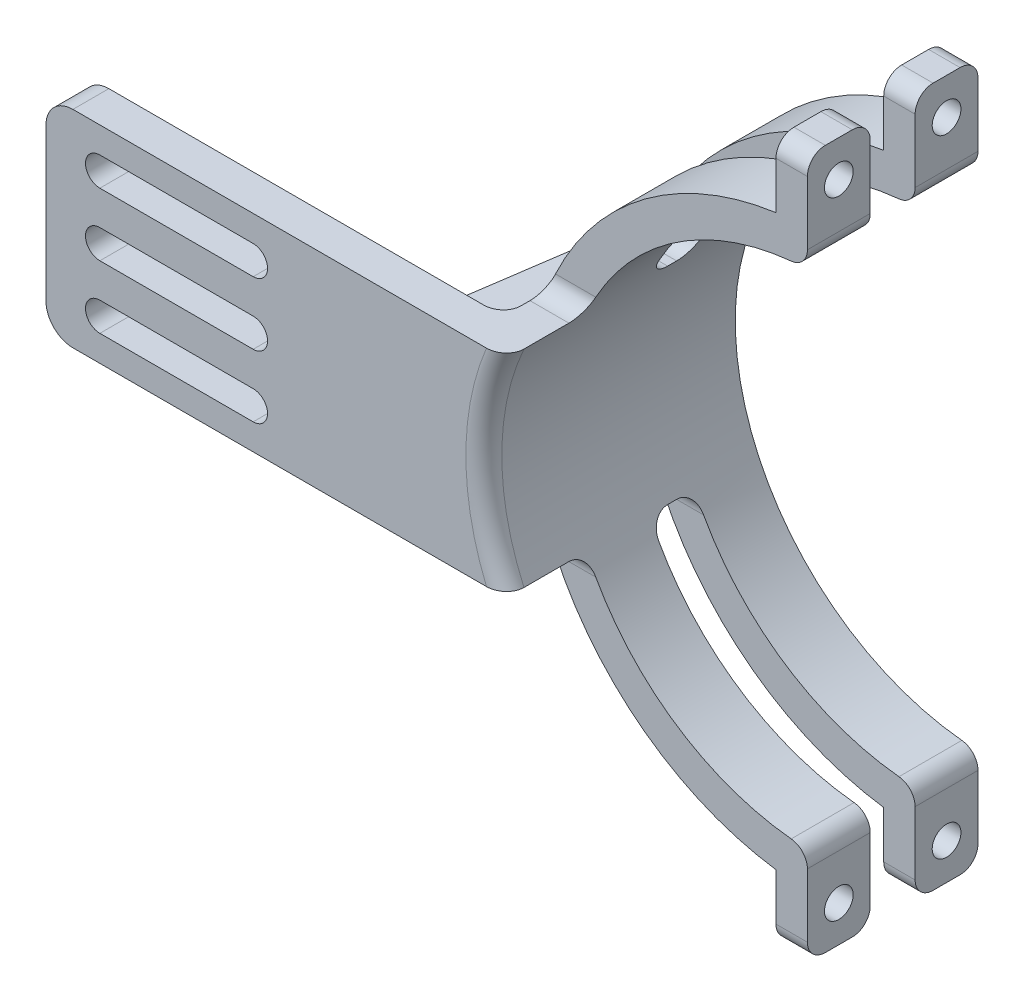
SolidWorks part; units mm, degrees
ref_plane "前视基准面" through (0, 0, 0) normal (0, 0, 1) x (1, 0, 0)
ref_plane "上视基准面" through (0, 0, 0) normal (0, 1, 0) x (1, 0, 0)
ref_plane "右视基准面" through (0, 0, 0) normal (1, 0, 0) x (0, 0, -1)
sketch "草图1" plane through (0, 0, 0) normal (0, 0, 1) x (1, 0, 0)
  line L0 (0, 148.5) -> (0, -94.9538) construction
  line L1 (105, -148.5) -> (-105, -148.5) construction
  line L2 (105, -148.5) -> (105, 148.5) construction
  line L3 (105, 148.5) -> (-105, 148.5) construction
  line L4 (-105, -148.5) -> (-105, 148.5) construction
  line L5 (105, -148.5) -> (-105, 148.5) construction
  line L6 (105, 148.5) -> (-105, -148.5) construction
  line L7 (35.8892, 121.6645) -> (-35.8892, 121.6645)
  line L8 (-35.8892, 121.6645) -> (-66.9017, 102.292)
  line L9 (-75, 40.9339) -> (-75, 31.2613)
  line L10 (-66.9017, 102.292) -> (-66.9017, 52.8701)
  line L11 (75, 40.9339) -> (75, 31.2613)
  line L12 (66.9017, 102.292) -> (66.9017, 52.8701)
  line L13 (35.8892, 121.6645) -> (66.9017, 102.292)
  line L14 (-75, 31.2613) -> (75, 31.2613)
  line L15 (-60, -148.5) -> (-60, -91.8129)
  line L16 (-75, 23.94) -> (75, 23.94)
  line L17 (-75, 23.94) -> (-75, 10.5626)
  line L18 (-38.8455, -105.5906) -> (-66.4608, -113.7617)
  line L19 (-66.4608, -113.7617) -> (-70.1743, -102.7328)
  line L20 (75, 23.94) -> (75, 10.5626)
  line L21 (66.4608, -113.7617) -> (70.1743, -102.7328)
  line L22 (38.8455, -105.5906) -> (66.4608, -113.7617)
  line L23 (-105, 93.0519) -> (105, 93.0519)
  line L24 (-105, 63.0519) -> (105, 63.0519)
  line L25 (-105, -90.0629) -> (-70.5337, -90.0629)
  line L26 (-105, -60.0629) -> (-67.4027, -60.0629)
  line L27 (60, -148.5) -> (60, 148.5)
  line L28 (-60, -58.3129) -> (-45, -58.3129)
  line L29 (-60, -61.8129) -> (-45, -61.8129)
  line L30 (-36, -58.3129) -> (-21, -58.3129)
  line L31 (-36, -61.8129) -> (-21, -61.8129)
  line L32 (-60, -88.3129) -> (-45, -88.3129)
  line L33 (-60, -91.8129) -> (-45, -91.8129)
  line L34 (-36, -88.3129) -> (-21, -88.3129)
  line L35 (-36, -91.8129) -> (-21, -91.8129)
  line L36 (-60, -58.3129) -> (-60, 148.5)
  line L37 (-19.25, -90.0629) -> (105, -90.0629)
  line L38 (-19.25, -60.0629) -> (19.25, -60.0629)
  line L39 (-60, -88.3129) -> (-60, -61.8129)
  line L40 (21, -58.3129) -> (36, -58.3129)
  line L41 (45, -58.3129) -> (60, -58.3129)
  line L42 (60, -61.8129) -> (45, -61.8129)
  line L43 (36, -61.8129) -> (21, -61.8129)
  line L44 (21, -88.3129) -> (36, -88.3129)
  line L45 (21, -91.8129) -> (36, -91.8129)
  line L46 (45, -88.3129) -> (60, -88.3129)
  line L47 (45, -91.8129) -> (60, -91.8129)
  line L48 (37.75, -60.0629) -> (43.25, -60.0629)
  line L49 (58.25, -60.0629) -> (105, -60.0629)
  line L50 (-60, 94.8019) -> (-45, 94.8019)
  line L51 (-36, 94.8019) -> (-21, 94.8019)
  line L52 (-60, 91.3019) -> (-45, 91.3019)
  line L53 (-36, 91.3019) -> (-21, 91.3019)
  line L54 (-60, 64.8019) -> (-45, 64.8019)
  line L55 (-60, 61.3019) -> (-45, 61.3019)
  line L56 (-36, 64.8019) -> (-21, 64.8019)
  line L57 (-36, 61.3019) -> (-21, 61.3019)
  line L58 (21, 94.8019) -> (36, 94.8019)
  line L59 (21, 91.3019) -> (36, 91.3019)
  line L60 (45, 94.8019) -> (60, 94.8019)
  line L61 (45, 91.3019) -> (60, 91.3019)
  line L62 (21, 61.3019) -> (36, 61.3019)
  line L63 (21, 64.8019) -> (36, 64.8019)
  line L64 (45, 61.3019) -> (60, 61.3019)
  line L65 (45, 64.8019) -> (60, 64.8019)
  line L66 (-33.1709, -104.7687) -> (33.1709, -104.7687)
  line L67 (0, -104.7687) -> (0, -148.5) construction
  arc A0 (-75, 40.9339) -> (-66.9017, 52.8701) centre (-79.7474, 52.8701) ccw
  arc A1 (75, 40.9339) -> (66.9017, 52.8701) centre (79.7474, 52.8701) cw
  arc A3 (-60, -88.3129) -> (-60, -91.8129) centre (-60, -90.0629) ccw
  arc A4 (-60, -58.3129) -> (-60, -61.8129) centre (-60, -60.0629) ccw
  circle A5 centre (-60, 63.0519) radius 1.75
  circle A6 centre (-60, 93.0519) radius 1.75
  circle A7 centre (60, 93.0519) radius 1.75
  circle A8 centre (60, 63.0519) radius 1.75
  arc A9 (60, -91.8129) -> (60, -88.3129) centre (60, -90.0629) ccw
  arc A10 (60, -61.8129) -> (60, -58.3129) centre (60, -60.0629) ccw
  arc A11 (-36, -58.3129) -> (-36, -61.8129) centre (-36, -60.0629) ccw
  arc A12 (-36, -88.3129) -> (-36, -91.8129) centre (-36, -90.0629) ccw
  arc A13 (36, -61.8129) -> (36, -58.3129) centre (36, -60.0629) ccw
  arc A14 (36, -91.8129) -> (36, -88.3129) centre (36, -90.0629) ccw
  arc A15 (-45, -61.8129) -> (-45, -58.3129) centre (-45, -60.0629) ccw
  arc A16 (-21, -61.8129) -> (-21, -58.3129) centre (-21, -60.0629) ccw
  arc A17 (-45, -91.8129) -> (-45, -88.3129) centre (-45, -90.0629) ccw
  arc A18 (-21, -91.8129) -> (-21, -88.3129) centre (-21, -90.0629) ccw
  arc A19 (45, -58.3129) -> (45, -61.8129) centre (45, -60.0629) ccw
  arc A20 (21, -58.3129) -> (21, -61.8129) centre (21, -60.0629) ccw
  arc A21 (21, -88.3129) -> (21, -91.8129) centre (21, -90.0629) ccw
  arc A22 (45, -88.3129) -> (45, -91.8129) centre (45, -90.0629) ccw
  circle A23 centre (-36, 93.0519) radius 1.75
  circle A24 centre (-36, 63.0519) radius 1.75
  circle A25 centre (36, 93.0519) radius 1.75
  circle A26 centre (36, 63.0519) radius 1.75
  circle A27 centre (-45, 93.0519) radius 1.75
  circle A28 centre (-21, 93.0519) radius 1.75
  circle A29 centre (-45, 63.0519) radius 1.75
  circle A30 centre (-21, 63.0519) radius 1.75
  circle A31 centre (21, 93.0519) radius 1.75
  circle A32 centre (21, 63.0519) radius 1.75
  circle A33 centre (45, 93.0519) radius 1.75
  circle A34 centre (45, 63.0519) radius 1.75
  arc A35 (33.1709, -104.7687) -> (38.8455, -105.5906) centre (33.1709, -124.7687) cw
  arc A36 (-33.1709, -104.7687) -> (-38.8455, -105.5906) centre (-33.1709, -124.7687) ccw
  spline S0 degree 3 poles (-75, 10.5626) (-72.6959, 1.9073) (-70.3396, -13.3728) (-67.1028, -43.6255) (-66.7657, -72.9327) (-71.8903, -95.1489) (-70.1743, -102.7328) knots 0 0 0 0 0.235247 0.406294 0.801186 1 1 1 1
  spline S1 degree 3 poles (75, 10.5626) (72.6959, 1.9073) (70.3396, -13.3728) (67.1028, -43.6255) (66.7657, -72.9327) (71.8903, -95.1489) (70.1743, -102.7328) knots 0 0 0 0 0.235247 0.406294 0.801186 1 1 1 1
  point P0 (0, 0)
  point P27 (0, 121.6645)
  point P42 (0, -94.0966)
  dimension "D1" = 60
  dimension "D4" = 20
  dimension "D5" = 24
  dimension "D7" = 24
  dimension "D9" = 15
  dimension "D10" = 15
  dimension "D13" = 24
  dimension "D17" = 15
  dimension "D2" = 30
  dimension "D3" = 30
  dimension "D6" = 24
  dimension "D8" = 24
  dimension "D11" = 15
  dimension "D12" = 15
  dimension "D14" = 24
  dimension "D15" = 24
  dimension "D16" = 24
  dimension "D18" = 15
  dimension "D19" = 15
  dimension "D20" = 15
  dimension "D21" = 15
  dimension "D22" = 15
  dimension "D23" = 15
  dimension "D24" = 15
  dimension "D25" = 15
  dimension "D26" = 15
  dimension "D27" = 15
  dimension "D28" = 15
  dimension "D29" = 3.5
  dimension "D30" = 3.5
  dimension "D31" = 3.5
extrude "凸台-拉伸1" add sketch "草图1" along normal blind 3 contours A34 L24 A26 L62 A32 A30 L57 A24 A29 L55 L36 L14 L27 L64 | A5 L24 L10 A0 L9 L14 L36 | A6 L23 L10 L24 A5 L36 | A6 L36 L8 L10 L23 | A33 L60 L27 L13 L7 L8 L36 L50 A27 L23 A23 L51 A28 A31 L58 A25 | A34 L65 L27 L61 A33 L23 A25 L59 A31 A28 L53 A23 A27 L52 L36 L54 A29 L24 A24 L56 A30 A32 L63 A26 | A7 L23 L12 L13 L27 | A8 L24 L12 L23 A7 L27 | A8 L27 L14 L11 A1 L12 L24 | A22 L46 L27 L42 A19 A13 L43 A20 A16 L31 A11 L30 L40 L41 L16 L36 L28 A15 L29 L39 L32 A17 L33 L15 L18 L22 L47 A14 L45 A21 A18 L35 A12 L34 | L17 S0 L19 L18 L15 A3 L39 A4 L36 L16 | S1 L20 L16 L27 A10 L49 | S1 L49 A10 L27 A9 L37 | S1 L37 A9 L27 L22 L21 region at (0, 106.7597, 0) region at (63.3118, 98.9762, 0) region at (-63.3118, 98.9762, 0) region at (63.5153, 78.0519, 0) region at (-63.5153, 78.0519, 0) region at (65.7633, 44.067, 0) region at (0, 78.0519, 0) region at (-65.7633, 44.067, 0) region at (0, 46.6707, 0) region at (0, -40.0712, 0) region at (65.6849, -11.6712, 0) region at (-65.3451, -38.0027, 0) region at (64.4303, -76.0355, 0) region at (65.0264, -100.7629, 0)
sketch "草图7" plane through (0, 0, 0) normal (0, 0, -1) x (-1, 0, 0)
  line L0 (0, 121.6645) -> (0, -104.7687) construction
  line L1 (-35.8892, 121.6645) -> (35.8892, 121.6645) construction
  line L2 (33.1709, -104.7687) -> (-33.1709, -104.7687) construction
  line L3 (0, 41.2613) -> (-21, 41.2613) construction
  line L4 (0, 41.2613) -> (21, 41.2613) construction
  line L5 (0, 13.94) -> (-21, 13.94) construction
  line L6 (0, 13.94) -> (21, 13.94) construction
  line L7 (75, 23.94) -> (-75, 23.94) construction
  line L8 (75, 31.2613) -> (-75, 31.2613) construction
  circle A0 centre (-21, 41.2613) radius 2.25
  circle A1 centre (21, 41.2613) radius 2.25
  circle A2 centre (-21, 13.94) radius 2.25
  circle A3 centre (21, 13.94) radius 2.25
  dimension "D1" = 10
  dimension "D2" = 10
extrude "切除-拉伸2" cut sketch "草图7" against normal through all
sketch "草图8" plane through (0, 0, 3) normal (0, 0, 1) x (1, 0, 0)
  line L0 (0, 121.6645) -> (0, -1.9696) construction
  line L1 (35.8892, 121.6645) -> (-35.8892, 121.6645) construction
  line L2 (-33.1709, -104.7687) -> (33.1709, -104.7687) construction
  line L3 (-33.409, 20.409) -> (-12.6214, -0.3786)
  line L4 (31.818, -51.182) -> (-31.818, -51.182)
  line L5 (35, -48) -> (35, 15.6418)
  line L8 (-35, 18.818) -> (-12.6214, -3.5605) construction
  line L9 (-33.409, -52.773) -> (-12.5737, -31.9377)
  line L10 (-36.591, 17.227) -> (-15.8034, -3.5605)
  line L11 (33.4105, 20.4105) -> (12.573, -0.427)
  line L12 (15.803, -3.5609) -> (36.5881, 17.2241)
  line L13 (31.8195, 18.8195) -> (-31.818, 18.818)
  line L14 (-15.8038, -28.8038) -> (-36.591, -49.591)
  line L15 (12.5534, -31.9174) -> (33.409, -52.773)
  line L16 (34.9993, 18.8173) -> (12.6207, -3.5613) construction
  line L17 (0, -30.3951) -> (0, -104.7687) construction
  line L18 (-35, -48) -> (-35, 15.636)
  line L19 (-11.9624, -1.9696) -> (-14.2124, -1.9696) construction
  line L20 (15.8034, -28.8034) -> (36.591, -49.591)
  line L21 (14.2117, -30.3951) -> (11.9607, -30.3951) construction
  line L22 (14.2117, -30.3951) -> (14.2117, -28.1441) construction
  line L23 (14.2117, -1.9696) -> (11.9612, -1.9696) construction
  line L24 (-14.2124, -30.3951) -> (-14.2124, -28.1446) construction
  line L25 (14.2117, -30.3951) -> (12.62, -28.8034) construction
  line L26 (14.2117, -1.9696) -> (12.6204, -3.5609) construction
  line L27 (12.6207, -28.8027) -> (35, -51.182) construction
  line L28 (-12.6215, -3.5606) -> (-14.2124, -1.9696) construction
  line L29 (-14.2124, -4.2196) -> (-14.2124, -1.9696) construction
  line L30 (-12.6214, -28.8034) -> (-35, -51.182) construction
  line L31 (-12.6211, -28.8037) -> (-14.2124, -30.3951) construction
  line L32 (-11.9619, -30.3951) -> (-14.2124, -30.3951) construction
  line L33 (14.2117, -4.2201) -> (14.2117, -1.9696) construction
  line L34 (11.0312, -30.3951) -> (0, -30.3951) construction
  arc A0 (-33.409, 20.409) -> (-36.591, 17.227) centre (-35, 18.818) ccw
  arc A1 (36.5881, 17.2241) -> (33.4105, 20.4105) centre (34.9993, 18.8173) ccw
  arc A2 (-36.591, -49.591) -> (-33.409, -52.773) centre (-35, -51.182) ccw
  arc A3 (33.409, -52.773) -> (36.591, -49.591) centre (35, -51.182) ccw
  arc A4 (-15.8034, -3.5605) -> (-12.6214, -0.3786) centre (-14.2124, -1.9696) ccw
  arc A5 (12.6692, -0.3308) -> (15.803, -3.5609) centre (14.2117, -1.9696) ccw
  arc A6 (-12.6699, -32.0338) -> (-15.8038, -28.8038) centre (-14.2124, -30.3951) ccw
  arc A7 (15.8034, -28.8034) -> (12.6894, -32.0534) centre (14.2117, -30.3951) ccw
  circle A8 centre (-0.0004, -16.1823) radius 8
  point P6 (0, -16.182)
  point P13 (-0.0004, -16.1823)
extrude "切除-拉伸3" cut sketch "草图8" against normal through all contours L10 A4 L3 A0 | L11 A5 L12 A1 | L20 A7 L15 A3 | L9 A6 L14 A2 | A8 region at (-24.6062, 8.4242, 3) region at (24.6054, 8.4234, 3) region at (-24.6061, -40.7881, 3) region at (24.6056, -40.7877, 3) region at (-0.0004, -16.1823, 3)
sketch "草图9" plane through (0, 0, 3) normal (0, 0, 1) x (1, 0, 0)
  line L0 (-70.7828, -98.747) -> (70.7828, -98.747) construction
  line L1 (0, -98.747) -> (0, -104.7687) construction
  line L2 (55, -100.497) -> (20, -100.497)
  line L3 (-55, -96.997) -> (-20, -96.997)
  line L4 (-55, -100.497) -> (-20, -100.497)
  line L5 (-33.1709, -104.7687) -> (33.1709, -104.7687) construction
  line L6 (55, -96.997) -> (20, -96.997)
  arc A0 (-55, -96.997) -> (-55, -100.497) centre (-55, -98.747) ccw
  arc A1 (-20, -100.497) -> (-20, -96.997) centre (-20, -98.747) ccw
  arc A2 (20, -100.497) -> (20, -96.997) centre (20, -98.747) cw
  arc A3 (55, -96.997) -> (55, -100.497) centre (55, -98.747) cw
  spline S0 degree 3 poles (-75, 10.5626) (-72.6959, 1.9073) (-70.3396, -13.3728) (-67.1028, -43.6255) (-66.7657, -72.9327) (-71.8903, -95.1489) (-70.1743, -102.7328) knots 0 0 0 0 0.235247 0.406294 0.801186 1 1 1 1 construction
  spline S1 degree 3 poles (75, 10.5626) (72.6959, 1.9073) (70.3396, -13.3728) (67.1028, -43.6255) (66.7657, -72.9327) (71.8903, -95.1489) (70.1743, -102.7328) knots 0 0 0 0 0.235247 0.406294 0.801186 1 1 1 1 construction
  dimension "D1" = 35
  dimension "D2" = 20
extrude "切除-拉伸4" cut sketch "草图9" against normal blind 3
sketch "草图10" plane through (0, 0, 3) normal (0, 0, 1) x (1, 0, 0)
  line L0 (-21, -60.0629) -> (-21, -90.0629) construction
  line L1 (21, -60.0629) -> (21, -90.0629) construction
  line L2 (-21, -75.0629) -> (-17.5, -75.0629) construction
  line L4 (12.5, -80.0629) -> (-12.5, -80.0629)
  line L6 (12.5, -70.0629) -> (-12.5, -70.0629)
  line L11 (17.5, -75.0629) -> (21, -75.0629) construction
  arc A0 (-12.5, -70.0629) -> (-12.5, -80.0629) centre (-12.5, -75.0629) ccw
  arc A1 (12.5, -80.0629) -> (12.5, -70.0629) centre (12.5, -75.0629) ccw
  point P11 (0, -75.0629)
extrude "切除-拉伸5" cut sketch "草图10" against normal blind 3
sketch "草图11" plane through (0, 0, 3) normal (0, 0, 1) x (1, 0, 0)
  line L0 (-21, 93.0519) -> (-21, 63.0519) construction
  line L1 (21, 93.0519) -> (21, 63.0519) construction
  line L2 (-21, 78.0519) -> (-20, 78.0519) construction
  line L4 (15, 73.0519) -> (-15, 73.0519)
  line L6 (15, 83.0519) -> (-15, 83.0519)
  line L10 (20, 78.0519) -> (21, 78.0519) construction
  arc A0 (-15, 83.0519) -> (-15, 73.0519) centre (-15, 78.0519) ccw
  arc A1 (15, 73.0519) -> (15, 83.0519) centre (15, 78.0519) ccw
  point P10 (0, 78.0519)
  dimension "D1" = 30
extrude "切除-拉伸8" cut sketch "草图11" against normal blind 3
sketch "草图12" plane through (0, 0, 3) normal (0, 0, 1) x (1, 0, 0)
  line L0 (0, 121.6645) -> (0, 83.0519) construction
  line L1 (35.8892, 121.6645) -> (-35.8892, 121.6645) construction
  line L2 (15, 83.0519) -> (-15, 83.0519) construction
  circle A0 centre (0, 106.3718) radius 11 construction
  circle A1 centre (0, 106.3718) radius 8 construction
  circle A2 centre (0, 114.3718) radius 1.7
  circle A3 centre (0, 98.3718) radius 1.7
  circle A4 centre (8, 106.3718) radius 1.7
  circle A5 centre (-8, 106.3718) radius 1.7
extrude "切除-拉伸9" cut sketch "草图12" against normal blind 3
sketch "草图13" plane through (0, 0, 3) normal (0, 0, 1) x (1, 0, 0)
  line L0 (0, -104.7687) -> (0, -80.0629) construction
  line L1 (-33.1709, -104.7687) -> (33.1709, -104.7687) construction
  line L2 (-12.5, -80.0629) -> (12.5, -80.0629) construction
  circle A0 centre (0, -92.4158) radius 8 construction
  circle A1 centre (0, -84.4158) radius 1.7
  circle A2 centre (8, -92.4158) radius 1.7
  circle A3 centre (0, -100.4158) radius 1.7
  circle A4 centre (-8, -92.4158) radius 1.7
extrude "切除-拉伸11" cut sketch "草图13" against normal blind 3
sketch "草图14" plane through (0, 0, 3) normal (0, 0, 1) x (1, 0, 0)
  line L0 (0, 23.94) -> (0, -104.7687) construction
  line L1 (-55.4755, 8.9197) -> (-55.4755, -46.0803)
  line L2 (-58.9755, 8.9197) -> (-58.9755, -46.0803)
  line L3 (-75, 23.94) -> (75, 23.94) construction
  line L4 (-33.1709, -104.7687) -> (33.1709, -104.7687) construction
  line L5 (58.9755, 8.9197) -> (58.9755, -46.0803)
  line L6 (55.4755, 8.9197) -> (55.4755, -46.0803)
  arc A0 (-55.4755, 8.9197) -> (-58.9755, 8.9197) centre (-57.2255, 8.9197) ccw
  arc A1 (-58.9755, -46.0803) -> (-55.4755, -46.0803) centre (-57.2255, -46.0803) ccw
  arc A2 (58.9755, -46.0803) -> (55.4755, -46.0803) centre (57.2255, -46.0803) cw
  arc A3 (55.4755, 8.9197) -> (58.9755, 8.9197) centre (57.2255, 8.9197) cw
extrude "切除-拉伸12" cut sketch "草图14" against normal through all
fillet "圆角1" radius 2 2 edges at (75, 31.2613, 1.5) (-75, 31.2613, 1.5)
fillet "圆角2" radius 2 2 edges at (-75, 23.94, 1.5) (75, 23.94, 1.5)
sketch "草图15" plane through (0, 0, 0) normal (0, 0, -1) x (-1, 0, 0)
  line L0 (0, 121.6645) -> (0, 31.2613) construction
  line L1 (-35.8892, 121.6645) -> (35.8892, 121.6645) construction
  line L2 (73, 31.2613) -> (-73, 31.2613) construction
  line L3 (-27.5188, 121.6645) -> (-63.6963, 99.0657) construction
  line L4 (-35.8892, 121.6645) -> (-66.9017, 102.292) construction
  line L5 (-61.1842, 102.4035) -> (-34.7748, 118.9006)
  line L6 (-59.5948, 99.8591) -> (-33.1854, 116.3562)
  line L7 (27.5188, 121.6645) -> (63.6963, 99.0657) construction
  line L8 (59.5948, 99.8591) -> (33.1854, 116.3562)
  line L9 (61.1842, 102.4035) -> (34.7748, 118.9006)
  arc A0 (-61.1842, 102.4035) -> (-59.5948, 99.8591) centre (-60.3895, 101.1313) ccw
  arc A1 (-33.1854, 116.3562) -> (-34.7748, 118.9006) centre (-33.9801, 117.6284) ccw
  arc A2 (33.1854, 116.3562) -> (34.7748, 118.9006) centre (33.9801, 117.6284) cw
  arc A3 (61.1842, 102.4035) -> (59.5948, 99.8591) centre (60.3895, 101.1313) cw
extrude "切除-拉伸13" cut sketch "草图15" against normal through all
sketch "草图16" plane through (0, 0, 0) normal (0, 0, -1) x (-1, 0, 0)
  line L0 (0, 121.6645) -> (0, 31.2613) construction
  line L1 (-35.8892, 121.6645) -> (35.8892, 121.6645) construction
  line L2 (73, 31.2613) -> (-73, 31.2613) construction
  line L3 (-21, 41.2613) -> (-66.71, 41.2613) construction
  line L4 (-61.517, 42.7613) -> (-32.0563, 42.7613)
  line L5 (-61.517, 39.7613) -> (-32.0563, 39.7613)
  line L6 (21, 41.2613) -> (66.71, 41.2613) construction
  line L7 (61.517, 39.7613) -> (32.0563, 39.7613)
  line L8 (61.517, 42.7613) -> (32.0563, 42.7613)
  arc A0 (-61.517, 42.7613) -> (-61.517, 39.7613) centre (-61.517, 41.2613) ccw
  arc A1 (-32.0563, 39.7613) -> (-32.0563, 42.7613) centre (-32.0563, 41.2613) ccw
  arc A2 (32.0563, 39.7613) -> (32.0563, 42.7613) centre (32.0563, 41.2613) cw
  arc A3 (61.517, 42.7613) -> (61.517, 39.7613) centre (61.517, 41.2613) cw
extrude "切除-拉伸14" cut sketch "草图16" against normal through all
sketch "草图17" plane through (0, 0, 0) normal (0, 0, -1) x (-1, 0, 0)
  text T0 "Y" font "黑体" height in points 72
extrude "切除-拉伸15" cut sketch "草图17" against normal through all
sketch "草图18" plane through (0, 0, 0) normal (0, 0, -1) x (-1, 0, 0)
  text T0 "H" font "黑体" height in points 72
extrude "切除-拉伸16" cut sketch "草图18" against normal through all
ref_plane "基准面1" through (0, 0, -10) normal (0, 0, -1) x (-1, 0, 0)
sketch "草图19" plane through (0, 0, -10) normal (0, 0, -1) x (-1, 0, 0)
  line L0 (-58.9755, -46.0803) -> (-58.9755, 8.9197) construction
  line L1 (-55.4755, 8.9197) -> (-55.4755, -46.0803) construction
  line L2 (-58.9755, -30.086) -> (-58.9755, -15.086)
  line L3 (-55.4755, -15.086) -> (-55.4755, -30.086)
  line L4 (-57.2255, -15.086) -> (-57.2255, -30.086) construction
  line L5 (-55.4755, -15.086) -> (-55.4755, -30.086)
  line L6 (-58.9755, -15.086) -> (-58.9755, -30.086)
  line L7 (-61.7255, -34.086) -> (-89.4178, -34.086) construction
  line L8 (-61.7255, -34.086) -> (-52.7255, -34.086)
  line L10 (-61.7255, -11.086) -> (-52.7255, -11.086)
  line L11 (-52.7255, -34.086) -> (-52.7255, -11.086)
  line L12 (-61.7255, -34.086) -> (-52.7255, -11.086) construction
  line L13 (-58.9755, -18.1137) -> (-52.7255, -34.086) construction
  line L14 (-75, 21.94) -> (-75, 10.5626) construction
  line L15 (-61.7255, -11.086) -> (-75, -11.086)
  line L17 (-61.7255, -34.086) -> (-75, -34.086)
  line L18 (-75, -11.086) -> (-75, -34.086)
  arc A0 (-58.9755, -46.0803) -> (-55.4755, -46.0803) centre (-57.2255, -46.0803) ccw construction
  arc A1 (-55.4755, 8.9197) -> (-58.9755, 8.9197) centre (-57.2255, 8.9197) ccw construction
  arc A2 (-58.9755, -46.0803) -> (-55.4755, -46.0803) centre (-57.2255, -46.0803) ccw
  arc A3 (-55.4755, 8.9197) -> (-58.9755, 8.9197) centre (-57.2255, 8.9197) ccw
  arc A4 (-55.4755, -15.086) -> (-58.9755, -15.086) centre (-57.2255, -15.086) ccw
  arc A5 (-58.9755, -30.086) -> (-55.4755, -30.086) centre (-57.2255, -30.086) ccw
  point P7 (-57.2255, -22.586)
  dimension "D1" = 15
  dimension "D2" = 0
extrude "凸台-拉伸2" add sketch "草图19" along normal blind 4 separate body contours L15 L18 L17 L8 L11 L10 A5 L2 A4 L3 region at (64.7786, -22.586, -10)
sketch "草图20" plane through (0, 0, -14) normal (0, 0, -1) x (-1, 0, 0)
  line L0 (-52.7255, -34.086) -> (-75, -34.086) construction
  line L1 (-75, -11.086) -> (-71, -11.086)
  line L2 (-75, -11.086) -> (-75, -34.086)
  line L3 (-75, -34.086) -> (-71, -34.086)
  line L4 (-71, -11.086) -> (-71, -34.086)
extrude "凸台-拉伸3" add sketch "草图20" along normal blind 5
sketch "草图21" plane through (0, 0, -19) normal (0, 0, -1) x (-1, 0, 0)
  line L0 (-71, -22.586) -> (-170.2086, -22.586) construction
  line L1 (-71, -34.086) -> (-71, -11.086) construction
  line L2 (-75, -11.086) -> (-75, -34.086) construction
  line L3 (-102.0333, -61.5135) -> (-98.5333, -61.5135)
  line L4 (-108.0333, 16.3416) -> (-108.0333, 4.9579)
  line L5 (-102.0333, 16.3416) -> (-102.0333, 5.3974)
  line L6 (-111.5333, 16.3416) -> (-111.5333, 8.2553)
  line L7 (-98.5333, 16.3416) -> (-98.5333, 9.1008)
  line L8 (-111.5333, 16.3416) -> (-108.0333, 16.3416)
  line L9 (-102.0333, 16.3416) -> (-98.5333, 16.3416)
  line L11 (-111.5333, -61.5135) -> (-108.0333, -61.5135)
  line L12 (-111.5333, -53.4272) -> (-111.5333, -61.5135)
  line L13 (-108.0333, -50.1298) -> (-108.0333, -61.5135)
  line L14 (-102.0333, -50.5693) -> (-102.0333, -61.5135)
  line L15 (-98.5333, -54.2727) -> (-98.5333, -61.5135)
  arc A0 (-108.0333, 4.9579) -> (-108.0333, -50.1298) centre (-103, -22.586) ccw
  arc A1 (-111.5333, 8.2553) -> (-111.5333, -53.4272) centre (-103, -22.586) ccw
  arc A2 (-102.0333, -50.5693) -> (-102.0333, 5.3974) centre (-103, -22.586) ccw
  arc A3 (-98.5333, -54.2727) -> (-98.5333, 9.1008) centre (-103, -22.586) ccw
  dimension "D1" = 3.5
  dimension "D2" = 3.5
  dimension "D3" = 6
extrude "凸台-拉伸4" add sketch "草图21" along normal blind 7
sketch "草图22" plane through (0, 0, -19) normal (0, 0, 1) x (1, 0, 0)
  line L0 (75, -22.586) -> (75, -34.086) construction
  line L1 (75, -34.086) -> (73.1378, -34.086) construction
  line L2 (98.5333, -54.2727) -> (98.5333, -61.5135) construction
  line L3 (98.5333, -61.5135) -> (102.0333, -61.5135) construction
  line L4 (102.0333, -61.5135) -> (102.0333, -50.5693) construction
  line L5 (73.1378, -11.086) -> (75, -11.086) construction
  line L6 (75, -11.086) -> (75, -22.586) construction
  line L7 (102.0333, 5.3974) -> (102.0333, 16.3416) construction
  line L8 (102.0333, 16.3416) -> (98.5333, 16.3416) construction
  line L9 (98.5333, 16.3416) -> (98.5333, 9.1008) construction
  line L10 (75, -22.586) -> (75, -34.086)
  line L11 (75, -34.086) -> (73.1378, -34.086)
  line L12 (98.5333, -54.2727) -> (98.5333, -61.5135)
  line L13 (98.5333, -61.5135) -> (102.0333, -61.5135)
  line L14 (102.0333, -61.5135) -> (102.0333, -50.5693)
  line L15 (73.1378, -11.086) -> (75, -11.086)
  line L16 (75, -11.086) -> (75, -22.586)
  line L17 (102.0333, 5.3974) -> (102.0333, 16.3416)
  line L18 (102.0333, 16.3416) -> (98.5333, 16.3416)
  line L19 (98.5333, 16.3416) -> (98.5333, 9.1008)
  line L20 (75, -11.086) -> (77.4706, -11.086)
  line L21 (75, -34.086) -> (77.4706, -34.086)
  arc A1 (75, -22.586) -> (102.0333, -50.5693) centre (103, -22.586) ccw construction
  arc A2 (102.0333, 5.3974) -> (75, -22.586) centre (103, -22.586) ccw construction
  arc A5 (75, -22.586) -> (77.4706, -34.086) centre (103, -22.586) ccw
  arc A6 (77.4706, -11.086) -> (75, -22.586) centre (103, -22.586) ccw
  line M9 (75, -11.086) -> (75, -22.586)
  arc M10 (75, -22.586) -> (102.0333, 5.3974) centre (103, -22.586) cw
extrude "凸台-拉伸5" add sketch "草图22" along normal up to surface (9 mm away) contours L20 M9 M10 | A5 L10 L21 region at (75.7352, -31.2369, -19) region at (75.7352, -13.935, -19) up to face at (57.2255, -22.586, -10)
sketch "草图23" plane through (0, 0, -19) normal (0, 0, -1) x (-1, 0, 0)
  line L0 (-71, -22.586) -> (-71, -11.086) construction
  line L1 (-71, -11.086) -> (-73.1378, -11.086) construction
  line L2 (-73.1378, -34.086) -> (-71, -34.086) construction
  line L3 (-71, -34.086) -> (-71, -22.586) construction
  line L4 (-71, -22.586) -> (-71, -11.086)
  line L5 (-71, -11.086) -> (-73.1378, -11.086)
  line L6 (-73.1378, -34.086) -> (-71, -34.086)
  line L7 (-71, -34.086) -> (-71, -22.586)
  arc A0 (-71, -22.586) -> (-73.1378, -11.086) centre (-103, -22.586) ccw construction
  arc A1 (-73.1378, -34.086) -> (-71, -22.586) centre (-103, -22.586) ccw construction
  arc A2 (-71, -22.586) -> (-73.1378, -11.086) centre (-103, -22.586) ccw
  arc A3 (-73.1378, -34.086) -> (-71, -22.586) centre (-103, -22.586) ccw
  arc M1 (-71, -22.586) -> (-73.1378, -34.086) centre (-103, -22.586) cw
  line M2 (-73.1378, -34.086) -> (-71, -34.086)
  line M3 (-71, -34.086) -> (-71, -22.586)
extrude "切除-拉伸17" cut sketch "草图23" against normal up to surface (5 mm away) contours A2 L4 L5 | M3 M1 M2 region at (71.6375, -13.9414, -19) region at (71.6375, -31.2305, -19) up to face at (61.8628, -22.586, -14)
sketch "草图24" plane through (0, 0, -26) normal (0, 0, -1) x (-1, 0, 0)
  line L0 (-73.1378, -11.086) -> (-77.4706, -11.086)
  line L1 (-73.1378, -34.086) -> (-77.4706, -34.086)
  line L6 (-102.0333, -50.5693) -> (-102.0333, -61.5135)
  line L7 (-102.0333, -61.5135) -> (-98.5333, -61.5135)
  line L8 (-98.5333, -61.5135) -> (-98.5333, -54.2727)
  line L9 (-98.5333, 9.1008) -> (-98.5333, 16.3416)
  line L10 (-98.5333, 16.3416) -> (-102.0333, 16.3416)
  line L11 (-102.0333, 16.3416) -> (-102.0333, 5.3974)
  line L12 (-102.0333, -50.5693) -> (-102.0333, -61.5135)
  line L13 (-102.0333, -61.5135) -> (-98.5333, -61.5135)
  line L14 (-98.5333, -61.5135) -> (-98.5333, -54.2727)
  line L15 (-98.5333, 9.1008) -> (-98.5333, 16.3416)
  line L16 (-98.5333, 16.3416) -> (-102.0333, 16.3416)
  line L17 (-102.0333, 16.3416) -> (-102.0333, 5.3974)
  arc A2 (-102.0333, -50.5693) -> (-102.0333, 5.3974) centre (-103, -22.586) ccw
  arc A3 (-98.5333, -54.2727) -> (-98.5333, 9.1008) centre (-103, -22.586) ccw
  arc A4 (-77.4706, -34.086) -> (-77.4706, -11.086) centre (-103, -22.586) ccw
  arc A5 (-73.1378, -34.086) -> (-73.1378, -11.086) centre (-103, -22.586) ccw
  arc M9 (-102.0333, 5.3974) -> (-102.0333, -50.5693) centre (-103, -22.586) cw
  arc M13 (-98.5333, -54.2727) -> (-98.5333, 9.1008) centre (-103, -22.586) ccw
  dimension "D1" = 0
extrude "凸台-拉伸6" add sketch "草图24" along normal blind 5 contours L1 L0 M13 M9 region at (73.7718, -22.586, -26)
sketch "草图25" plane through (0, 0, -31) normal (0, 0, -1) x (-1, 0, 0)
  line L0 (-111.5333, -53.4272) -> (-111.5333, -61.5135) construction
  line L1 (-111.5333, -61.5135) -> (-108.0333, -61.5135) construction
  line L2 (-108.0333, -61.5135) -> (-108.0333, -50.1298) construction
  line L3 (-108.0333, 4.9579) -> (-108.0333, 16.3416) construction
  line L4 (-108.0333, 16.3416) -> (-111.5333, 16.3416) construction
  line L5 (-111.5333, 16.3416) -> (-111.5333, 8.2553) construction
  line L6 (-73.1378, -34.086) -> (-77.4706, -34.086) construction
  line L7 (-102.0333, -50.5693) -> (-102.0333, -61.5135) construction
  line L8 (-102.0333, -61.5135) -> (-98.5333, -61.5135) construction
  line L9 (-98.5333, -61.5135) -> (-98.5333, -54.2727) construction
  line L10 (-77.4706, -34.086) -> (-73.1378, -34.086) construction
  line L11 (-73.1378, -11.086) -> (-77.4706, -11.086) construction
  line L12 (-77.4706, -11.086) -> (-73.1378, -11.086) construction
  line L13 (-98.5333, 9.1008) -> (-98.5333, 16.3416) construction
  line L14 (-98.5333, 16.3416) -> (-102.0333, 16.3416) construction
  line L15 (-102.0333, 16.3416) -> (-102.0333, 5.3974) construction
  line L16 (-111.5333, -53.4272) -> (-111.5333, -61.5135)
  line L17 (-111.5333, -61.5135) -> (-108.0333, -61.5135)
  line L18 (-108.0333, -61.5135) -> (-108.0333, -50.1298)
  line L19 (-108.0333, 4.9579) -> (-108.0333, 16.3416)
  line L20 (-108.0333, 16.3416) -> (-111.5333, 16.3416)
  line L21 (-111.5333, 16.3416) -> (-111.5333, 8.2553)
  line L22 (-73.1378, -34.086) -> (-77.4706, -34.086)
  line L23 (-102.0333, -50.5693) -> (-102.0333, -61.5135)
  line L24 (-102.0333, -61.5135) -> (-98.5333, -61.5135)
  line L25 (-98.5333, -61.5135) -> (-98.5333, -54.2727)
  line L26 (-77.4706, -34.086) -> (-73.1378, -34.086)
  line L27 (-73.1378, -11.086) -> (-77.4706, -11.086)
  line L28 (-77.4706, -11.086) -> (-73.1378, -11.086)
  line L29 (-98.5333, 9.1008) -> (-98.5333, 16.3416)
  line L30 (-98.5333, 16.3416) -> (-102.0333, 16.3416)
  line L31 (-102.0333, 16.3416) -> (-102.0333, 5.3974)
  arc A0 (-111.5333, 8.2553) -> (-111.5333, -53.4272) centre (-103, -22.586) ccw construction
  arc A1 (-108.0333, 4.9579) -> (-108.0333, -50.1298) centre (-103, -22.586) ccw construction
  arc A2 (-98.5333, -54.2727) -> (-73.1378, -34.086) centre (-103, -22.586) ccw construction
  arc A3 (-102.0333, -50.5693) -> (-77.4706, -34.086) centre (-103, -22.586) ccw construction
  arc A4 (-73.1378, -34.086) -> (-73.1378, -11.086) centre (-103, -22.586) ccw construction
  arc A5 (-77.4706, -34.086) -> (-77.4706, -11.086) centre (-103, -22.586) ccw construction
  arc A6 (-73.1378, -11.086) -> (-98.5333, 9.1008) centre (-103, -22.586) ccw construction
  arc A7 (-77.4706, -11.086) -> (-102.0333, 5.3974) centre (-103, -22.586) ccw construction
  arc A8 (-111.5333, 8.2553) -> (-111.5333, -53.4272) centre (-103, -22.586) ccw
  arc A9 (-108.0333, 4.9579) -> (-108.0333, -50.1298) centre (-103, -22.586) ccw
  arc A10 (-98.5333, -54.2727) -> (-73.1378, -34.086) centre (-103, -22.586) ccw
  arc A11 (-102.0333, -50.5693) -> (-77.4706, -34.086) centre (-103, -22.586) ccw
  arc A12 (-73.1378, -34.086) -> (-73.1378, -11.086) centre (-103, -22.586) ccw
  arc A13 (-77.4706, -34.086) -> (-77.4706, -11.086) centre (-103, -22.586) ccw
  arc A14 (-73.1378, -11.086) -> (-98.5333, 9.1008) centre (-103, -22.586) ccw
  arc A15 (-77.4706, -11.086) -> (-102.0333, 5.3974) centre (-103, -22.586) ccw
  line M1 (-77.4706, -34.086) -> (-73.1378, -34.086)
  arc M2 (-73.1378, -34.086) -> (-73.1378, -11.086) centre (-103, -22.586) ccw
  line M3 (-73.1378, -11.086) -> (-77.4706, -11.086)
  arc M4 (-77.4706, -11.086) -> (-77.4706, -34.086) centre (-103, -22.586) cw
extrude "凸台-拉伸7" add sketch "草图25" along normal blind 7 contours A15 A14 L29 L30 L31 M3 | M4 M1 M2 M3 | A11 L23 L24 L25 A10 M1 | A9 L19 L20 L21 A8 L16 L17 L18 region at (134.1761, -22.586, -31) region at (88.8692, -47.8069, -31) region at (73.7718, -22.586, -31) region at (88.8692, 2.635, -31)
sketch "草图26" plane through (111.5333, 0, 0) normal (1, 0, 0) x (0, 0, -1)
  line L0 (10, -22.586) -> (38, -22.586) construction
  line L1 (10, -11.086) -> (10, -34.086) construction
  line L2 (38, -53.4272) -> (38, 8.2553) construction
  line L3 (22.5, -61.5135) -> (22.5, -53.4272) construction
  line L4 (26, -61.5135) -> (19, -61.5135) construction
  line L5 (26, -53.4272) -> (19, -53.4272) construction
  line L6 (34.5, -61.5135) -> (34.5, -53.4272) construction
  line L7 (38, -61.5135) -> (31, -61.5135) construction
  line L8 (38, -53.4272) -> (31, -53.4272) construction
  circle A0 centre (22.5, -57.4704) radius 1.6
  circle A1 centre (34.5, -57.4704) radius 1.6
  circle A2 centre (34.5, 12.2985) radius 1.6
  circle A3 centre (22.5, 12.2985) radius 1.6
extrude "切除-拉伸18" cut sketch "草图26" against normal blind 27
fillet "圆角3" radius 2 1 edges at (71, -22.586, -14)
fillet "圆角4" radius 2 1 edges at (75, -22.586, -10)
fillet "圆角5" radius 2 4 edges at (75.3042, -11.086, -31) (75.3042, -11.086, -26) (75.3042, -34.086, -31) (75.3042, -34.086, -26)
fillet "圆角6" radius 2 2 edges at (75.3042, -11.086, -19) (75.3042, -34.086, -19)
fillet "圆角7" radius 2 8 edges at (100.2833, 16.3416, -38) (100.2833, 16.3416, -31) (100.2833, 16.3416, -26) (100.2833, 16.3416, -19) (100.2833, -61.5135, -38) (100.2833, -61.5135, -31) (100.2833, -61.5135, -26) (100.2833, -61.5135, -19)
fillet "圆角8" radius 2 4 edges at (109.7833, 16.3416, -26) (109.7833, 16.3416, -19) (109.7833, -61.5135, -26) (109.7833, -61.5135, -19)
fillet "圆角9" radius 2 4 edges at (109.7833, -61.5135, -38) (109.7833, -61.5135, -31) (109.7833, 16.3416, -38) (109.7833, 16.3416, -31)
fillet "圆角10" radius 2 4 edges at (102.0333, 5.3974, -34.5) (102.0333, 5.3974, -22.5) (102.0333, -50.5693, -34.5) (102.0333, -50.5693, -22.5)
fillet "圆角11" radius 2 2 edges at (108.0333, -50.1298, -22.5) (108.0333, 4.9579, -22.5)
fillet "圆角12" radius 2 2 edges at (108.0333, 4.9579, -34.5) (108.0333, -50.1298, -34.5)
sketch "草图27" plane through (0, 0, 0) normal (1, 0, 0) x (0, 0, -1)
  line L1 (-12.6568, -133.0679) -> (5.6125, -133.0679)
  line L2 (-12.6568, -133.0679) -> (-12.6568, 129.4587)
  line L3 (-12.6568, 129.4587) -> (5.6125, 129.4587)
  line L4 (5.6125, -133.0679) -> (5.6125, 129.4587)
extrude "切除-拉伸19" cut sketch "草图27" against normal through all and the other way through all
sketch "草图29" plane through (0, 0, -10) normal (0, 0, 1) x (1, 0, 0)
  line L0 (52.7255, -11.086) -> (10.9258, -11.086) construction
  line L1 (52.7255, -34.086) -> (75.2917, -34.086) construction
  line L2 (62.5652, -34.086) -> (42.7255, -34.086)
  line L3 (62.5652, -34.086) -> (62.5652, -11.086)
  line L4 (62.5652, -11.086) -> (42.7255, -11.086)
  line L5 (42.7255, -34.086) -> (42.7255, -11.086)
  line L6 (52.7255, -34.086) -> (52.7255, -11.086) construction
  dimension "D1" = 10
extrude "凸台-拉伸8" add sketch "草图29" against normal up to surface (4 mm away) up to face at (61.3637, -22.586, -14)
sketch "草图30" plane through (0, 0, -10) normal (0, 0, 1) x (1, 0, 0)
  line L0 (42.7255, -22.586) -> (73, -22.586) construction
  line L1 (42.7255, -11.086) -> (42.7255, -34.086) construction
  line L2 (42.7255, -30.586) -> (88.7938, -30.586) construction
  line L3 (59.7255, -32.186) -> (46.7255, -32.186)
  line L4 (59.7255, -28.986) -> (46.7255, -28.986)
  line L5 (59.7255, -16.186) -> (46.7255, -16.186)
  line L6 (59.7255, -12.986) -> (46.7255, -12.986)
  line L7 (59.7255, -24.186) -> (46.7255, -24.186)
  line L8 (59.7255, -20.986) -> (46.7255, -20.986)
  arc A0 (75.2917, -11.086) -> (75.2917, -34.086) centre (103, -22.586) ccw construction
  arc A1 (46.7255, -28.986) -> (46.7255, -32.186) centre (46.7255, -30.586) ccw
  arc A2 (59.7255, -32.186) -> (59.7255, -28.986) centre (59.7255, -30.586) ccw
  arc A3 (59.7255, -12.986) -> (59.7255, -16.186) centre (59.7255, -14.586) cw
  arc A4 (46.7255, -16.186) -> (46.7255, -12.986) centre (46.7255, -14.586) cw
  arc A5 (59.7255, -24.186) -> (59.7255, -20.986) centre (59.7255, -22.586) ccw
  arc A6 (46.7255, -20.986) -> (46.7255, -24.186) centre (46.7255, -22.586) ccw
  dimension "D2" = 4
  dimension "D1" = 8
  dimension "D3" = 13
  dimension "D4" = 2
extrude "切除-拉伸21" cut sketch "草图30" against normal blind 10
fillet "圆角13" radius 3 2 edges at (42.7255, -34.086, -12) (42.7255, -11.086, -12)
ref_plane "基准面2" through (0, -14.586, 0) normal (0, 1, 0) x (1, 0, 0)
sketch "草图32" plane through (0, 0, -38) normal (0, 0, -1) x (-1, 0, 0)
  line L0 (17.6561, -14.586) -> (-17.6561, -14.586) construction
  line L1 (-72.0161, -14.586) -> (-65.0863, -14.586)
  line L2 (-72.0161, -14.586) -> (-72.0161, -17.586)
  line L3 (-72.0161, -17.586) -> (-65.0863, -17.586)
  line L4 (-65.0863, -14.586) -> (-65.0863, -17.586)
  arc A0 (-73.1378, -34.086) -> (-73.1378, -11.086) centre (-103, -22.586) ccw construction
extrude "凸台-拉伸9" add sketch "草图32" against normal up to surface (24 mm away) up to face at (53.2255, -14.586, -14)
sketch "草图33" plane through (0, -14.586, 0) normal (0, 1, 0) x (1, 0, 0)
  line L0 (68.6192, 38) -> (65.0863, 14) construction
  line L1 (65.0863, 38) -> (72.0161, 38) construction
  line L2 (65.0863, 14) -> (65.0863, 38) construction
  line L3 (45.7255, 14) -> (71.0039, 14) construction
  line L4 (68.6192, 38) -> (65.0863, 14)
  line L5 (65.0863, 14) -> (65.0863, 38)
  line L6 (65.0863, 38) -> (68.6192, 38)
extrude "切除-拉伸22" cut sketch "草图33" against normal blind 10
sketch "草图35" plane through (0, 0, -10) normal (0, 0, 1) x (1, 0, 0)
  line L0 (42.7255, -14.086) -> (42.7255, -31.086) construction
  point P0 (42.7255, -22.586)
  point P1 (0, 0)
ref_plane "基准面3" through (0, -22.586, 0) normal (0, 1, 0) x (1, 0, 0)
mirror "镜向1" about plane through (0, -22.586, 0) normal (0, 1, 0) of "凸台-拉伸9"
mirror "镜向2" about plane through (0, -22.586, 0) normal (0, 1, 0) of "切除-拉伸22"
fillet "圆角14" radius 3 2 edges at (68.6192, -29.086, -38) (68.6192, -16.086, -38)
sketch "草图40" plane through (0, 0, -10) normal (0, 0, 1) x (1, 0, 0)
  line L0 (45.7255, -11.086) -> (21.3747, -11.086) construction
  line L2 (45.7255, -34.086) -> (75.2917, -34.086) construction
  line L3 (42.7255, -34.086) -> (26.2431, -34.086)
  line L5 (42.7255, -11.086) -> (26.2431, -11.086)
  line L6 (26.2431, -34.086) -> (26.2431, -11.086)
  line L9 (26.2431, -11.086) -> (62.0561, -11.086)
  line L10 (26.2431, -11.086) -> (26.2431, -34.086)
  line L11 (26.2431, -34.086) -> (62.0561, -34.086)
  line L12 (62.0561, -11.086) -> (62.0561, -34.086)
  point P3 (36.7255, -22.586)
  line M11 (46.7255, -12.986) -> (59.7255, -12.986)
  arc M12 (59.7255, -12.986) -> (59.7255, -16.186) centre (59.7255, -14.586) cw
  line M13 (59.7255, -16.186) -> (46.7255, -16.186)
  arc M14 (46.7255, -16.186) -> (46.7255, -12.986) centre (46.7255, -14.586) cw
  line M15 (46.7255, -28.986) -> (59.7255, -28.986)
  arc M16 (59.7255, -28.986) -> (59.7255, -32.186) centre (59.7255, -30.586) cw
  line M17 (59.7255, -32.186) -> (46.7255, -32.186)
  arc M18 (46.7255, -32.186) -> (46.7255, -28.986) centre (46.7255, -30.586) cw
  line M19 (46.7255, -20.986) -> (59.7255, -20.986)
  arc M20 (59.7255, -20.986) -> (59.7255, -24.186) centre (59.7255, -22.586) cw
  line M21 (59.7255, -24.186) -> (46.7255, -24.186)
  arc M22 (46.7255, -24.186) -> (46.7255, -20.986) centre (46.7255, -22.586) cw
  line M23 (42.7255, -14.086) -> (42.7255, -31.086)
  arc M24 (42.7255, -31.086) -> (45.7255, -34.086) centre (45.7255, -31.086) ccw
  line M25 (45.7255, -34.086) -> (75.2917, -34.086)
  line M27 (75.2917, -11.086) -> (45.7255, -11.086)
  arc M28 (45.7255, -11.086) -> (42.7255, -14.086) centre (45.7255, -14.086) ccw
extrude "凸台-拉伸10" add sketch "草图40" against normal up to surface (4 mm away) contours L3 L11 L9 L5 L6 M24 M23 M28 | L12 M27 M28 M23 M24 M25 M22 M19 M20 M21 M18 M15 M16 M17 M14 M11 M12 M13 region at (34.5742, -22.586, -10) region at (43.8166, -32.9948, -10) up to face at (53.2255, -14.586, -14)
sketch "草图41" plane through (0, 0, -10) normal (0, 0, 1) x (1, 0, 0)
  line L0 (61.3255, -14.586) -> (26.2431, -14.586) construction
  line L1 (26.2431, -34.086) -> (26.2431, -11.086) construction
  line L2 (61.3255, -22.586) -> (26.2431, -22.586) construction
  line L3 (61.3255, -30.586) -> (26.2431, -30.586) construction
  arc A0 (59.7255, -16.186) -> (59.7255, -12.986) centre (59.7255, -14.586) ccw construction
  arc A1 (59.7255, -24.186) -> (59.7255, -20.986) centre (59.7255, -22.586) ccw construction
  arc A2 (59.7255, -32.186) -> (59.7255, -28.986) centre (59.7255, -30.586) ccw construction
sketch "草图42" plane through (0, 0, -10) normal (0, 0, 1) x (1, 0, 0)
  line L0 (26.2431, -11.086) -> (75.2917, -11.086) construction
  line L1 (43.0618, -11.086) -> (64.7714, -11.086)
  line L2 (43.0618, -11.086) -> (43.0618, -34.086)
  line L3 (43.0618, -34.086) -> (64.7714, -34.086)
  line L4 (64.7714, -11.086) -> (64.7714, -34.086)
  line L5 (26.2431, -34.086) -> (75.2917, -34.086) construction
extrude "凸台-拉伸11" add sketch "草图42" against normal up to surface (4 mm away) up to face at (61.0853, -22.586, -14)
sketch "草图43" plane through (0, 0, -10) normal (0, 0, 1) x (1, 0, 0)
  line L0 (26.2431, -22.586) -> (73, -22.586) construction
  line L1 (26.2431, -34.086) -> (26.2431, -11.086) construction
  line L2 (26.2431, -15.586) -> (73.8281, -15.586) construction
  line L3 (26.2431, -29.586) -> (73.8281, -29.586) construction
  line L4 (32.2431, -15.586) -> (32.2431, -29.586) construction
  line L5 (49.3154, -15.586) -> (49.3154, -29.586) construction
  line L6 (32.2431, -13.986) -> (49.3154, -13.986)
  line L7 (32.2431, -17.186) -> (49.3154, -17.186)
  line L8 (32.2431, -20.986) -> (49.3154, -20.986)
  line L9 (32.2431, -24.186) -> (49.3154, -24.186)
  line L10 (32.2431, -27.986) -> (49.3154, -27.986)
  line L11 (32.2431, -31.186) -> (49.3154, -31.186)
  arc A0 (75.2917, -11.086) -> (75.2917, -34.086) centre (103, -22.586) ccw construction
  arc A1 (32.2431, -13.986) -> (32.2431, -17.186) centre (32.2431, -15.586) ccw
  arc A2 (32.2431, -20.986) -> (32.2431, -24.186) centre (32.2431, -22.586) ccw
  arc A3 (32.2431, -27.986) -> (32.2431, -31.186) centre (32.2431, -29.586) ccw
  arc A4 (49.3154, -17.186) -> (49.3154, -13.986) centre (49.3154, -15.586) ccw
  arc A5 (49.3154, -24.186) -> (49.3154, -20.986) centre (49.3154, -22.586) ccw
  arc A6 (49.3154, -31.186) -> (49.3154, -27.986) centre (49.3154, -29.586) ccw
  dimension "D3" = 6
  dimension "D1" = 7
  dimension "D2" = 7
extrude "切除-拉伸23" cut sketch "草图43" against normal blind 10
fillet "圆角15" radius 3 2 edges at (26.2431, -11.086, -12) (26.2431, -34.086, -12)
sketch "草图44" plane through (0, 0, -19) normal (0, 0, 1) x (1, 0, 0)
  line L1 (105.2213, -65.9928) -> (136.5164, -65.9928)
  line L2 (105.2213, -65.9928) -> (105.2213, 29.8483)
  line L3 (105.2213, 29.8483) -> (136.5164, 29.8483)
  line L4 (136.5164, -65.9928) -> (136.5164, 29.8483)
extrude "切除-拉伸24" cut sketch "草图44" against normal blind 30
